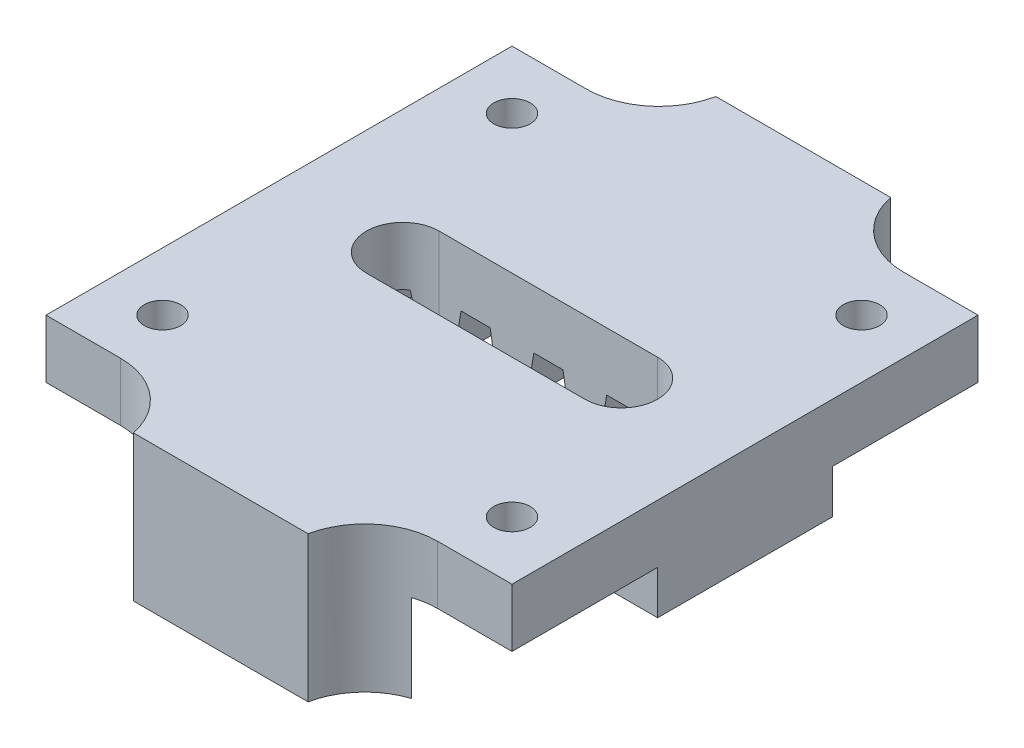
SolidWorks part; units mm, degrees
material "PBT Общее назначение"
ref_plane "Спереди" through (0, 0, 0) normal (0, 0, 1) x (1, 0, 0)
ref_plane "Сверху" through (0, 0, 0) normal (0, 1, 0) x (1, 0, 0)
ref_plane "Справа" through (0, 0, 0) normal (1, 0, 0) x (0, 0, -1)
sketch "Эскиз1" plane through (0, 0, 0) normal (0, 1, 0) x (1, 0, 0)
  line L0 (0, 0) -> (32, 0)
  line L1 (0, 0) -> (0, 32)
  line L2 (32, 0) -> (32, 32)
  line L3 (0, 32) -> (32, 32)
  dimension "D1" = 32
  dimension "D2" = 32
extrude "Бобышка-Вытянуть1" add sketch "Эскиз1" along normal blind 7
sketch "Эскиз3" plane through (0, 7, 0) normal (0, 1, 0) x (1, 0, 0)
  line L0 (16, 32) -> (16, 0) construction
  line L1 (32, 32) -> (0, 32) construction
  line L2 (0, 0) -> (32, 0) construction
  line L3 (32, 16) -> (0, 16) construction
  line L4 (32, 0) -> (32, 32) construction
  line L5 (0, 32) -> (0, 0) construction
  line L6 (4, 28) -> (28, 28) construction
  line L7 (4, 28) -> (4, 4) construction
  line L8 (28, 28) -> (28, 4) construction
  line L9 (4, 4) -> (28, 4) construction
  circle A0 centre (4, 28) radius 1.25
  circle A1 centre (28, 28) radius 1.25
  circle A2 centre (4, 4) radius 1.25
  circle A3 centre (28, 4) radius 1.25
  point P12 (16, 28)
  point P15 (28, 16)
  dimension "D3" = 2.5
  dimension "D1" = 24
  dimension "D2" = 24
extrude "Вырез-Вытянуть1" cut sketch "Эскиз3" against normal through all
sketch "Эскиз4" plane through (0, 0, 0) normal (0, -1, 0) x (1, 0, 0)
  line L0 (16, 0) -> (16, -32) construction
  line L1 (0, 0) -> (32, 0) construction
  line L2 (32, -32) -> (0, -32) construction
  line L3 (32, -16) -> (0, -16) construction
  line L4 (32, 0) -> (32, -32) construction
  line L5 (0, -32) -> (0, 0) construction
  line L6 (28, -10) -> (32, -10)
  line L7 (22, -4) -> (22, 0)
  line L8 (32, 0) -> (32, -10)
  line L9 (4, -10) -> (0, -10)
  line L10 (22, 0) -> (32, 0)
  line L11 (0, 0) -> (0, -10)
  line L12 (10, -4) -> (10, 0)
  line L13 (10, 0) -> (0, 0)
  line L14 (22, -32) -> (32, -32)
  line L15 (32, -32) -> (32, -22)
  line L16 (22, -28) -> (22, -32)
  line L17 (28, -22) -> (32, -22)
  line L18 (10, -32) -> (0, -32)
  line L19 (10, -28) -> (10, -32)
  line L20 (0, -32) -> (0, -22)
  line L21 (4, -22) -> (0, -22)
  arc A0 (22, -4) -> (28, -10) centre (28, -4) ccw
  arc A1 (10, -4) -> (4, -10) centre (4, -4) cw
  arc A2 (22, -28) -> (28, -22) centre (28, -28) cw
  arc A3 (10, -28) -> (4, -22) centre (4, -28) ccw
  dimension "D1" = 12
extrude "Вырез-Вытянуть2" cut sketch "Эскиз4" against normal blind 3
sketch "Эскиз5" plane through (0, 7, 0) normal (0, 1, 0) x (1, 0, 0)
  line L0 (16, 32) -> (16, 0) construction
  line L1 (32, 32) -> (0, 32) construction
  line L2 (0, 0) -> (32, 0) construction
  line L3 (32, 16) -> (0, 16) construction
  line L4 (32, 0) -> (32, 32) construction
  line L5 (0, 32) -> (0, 0) construction
  line L6 (23.5, 18.5) -> (8.5, 18.5)
  line L9 (23.5, 13.5) -> (8.5, 13.5)
  circle A0 centre (16, 16) radius 2.5 construction
  arc A1 (23.5, 13.5) -> (23.5, 18.5) centre (23.5, 16) ccw
  arc A2 (8.5, 18.5) -> (8.5, 13.5) centre (8.5, 16) ccw
  dimension "D1" = 5
  dimension "D2" = 7.5
  dimension "D3" = 7.5
extrude "Вырез-Вытянуть3" cut sketch "Эскиз5" against normal through all
sketch "Эскиз6" plane through (0, 0, 0) normal (0, 0, 1) x (1, 0, 0)
  line L0 (10, 7) -> (22, 7)
  line L1 (10, 7) -> (10, -3)
  line L2 (22, 7) -> (22, -3)
  line L3 (10, -3) -> (22, -3)
  line L4 (0, 7) -> (32, 7) construction
  line L5 (10, 3) -> (10, 0) construction
  line L6 (22, 3) -> (22, 0) construction
  line L7 (10, 0) -> (22, 0) construction
  dimension "D1" = 3
extrude "Бобышка-Вытянуть2" add sketch "Эскиз6" along normal blind 4
sketch "Эскиз7" plane through (0, 7, 0) normal (0, 1, 0) x (1, 0, 0)
  line L0 (32, 16) -> (0, 16) construction
  line L1 (32, 0) -> (32, 32) construction
  line L2 (0, 32) -> (0, 0) construction
ref_plane "Плоскость1" through (0, 0, -16) normal (0, 0, -1) x (-1, 0, 0)
mirror "Зеркальное отражение1" about plane through (0, 0, -16) normal (0, 0, -1) of "Бобышка-Вытянуть2"
sketch "Эскиз9" plane through (0, 7, 0) normal (0, 1, 0) x (1, 0, 0)
  line L0 (23.5, 16) -> (8.5, 16) construction
  line L1 (23.5, 10) -> (8.5, 10)
  line L2 (23.5, 22) -> (8.5, 22)
  arc A0 (23.5, 10) -> (23.5, 22) centre (23.5, 16) ccw
  arc A1 (8.5, 22) -> (8.5, 10) centre (8.5, 16) ccw
  arc A2 (8.5, 18.5) -> (8.5, 13.5) centre (8.5, 16) ccw construction
  point P3 (16, 16)
  dimension "D1" = 12
sketch "Эскиз10" plane through (0, 0, -16) normal (0, 0, -1) x (-1, 0, 0)
  line L1 (0, 0) -> (-4, 0) construction
  line L2 (0, 0) -> (-32, 0) construction
  line L4 (-16, 0) -> (-16, 31.1305) construction
  line L5 (-14.5, 0) -> (-15, 3)
  line L6 (-15, 3) -> (-17, 3)
  line L7 (-14.5, 0) -> (-17.5, 0)
  line L8 (-17.5, 0) -> (-17, 3)
  line L9 (-9.5, 0) -> (-10, 3)
  line L10 (-10, 3) -> (-12, 3)
  line L11 (-9.5, 0) -> (-12.5, 0)
  line L12 (-12.5, 0) -> (-12, 3)
  line L13 (-4.5, 0) -> (-5, 3)
  line L14 (-5, 3) -> (-7, 3)
  line L15 (-4.5, 0) -> (-7.5, 0)
  line L16 (-7.5, 0) -> (-7, 3)
  line L17 (-22.5, 0) -> (-22, 3)
  line L18 (-19.5, 0) -> (-22.5, 0)
  line L19 (-19.5, 0) -> (-20, 3)
  line L20 (-20, 3) -> (-22, 3)
  line L21 (-27.5, 0) -> (-27, 3)
  line L22 (-24.5, 0) -> (-27.5, 0)
  line L23 (-24.5, 0) -> (-25, 3)
  line L24 (-25, 3) -> (-27, 3)
  point P10 (-16, 3)
  point P16 (-11, 3)
  point P21 (-6, 3)
  dimension "D1" = 1.5
  dimension "D2" = 1
  dimension "D3" = 3
  dimension "D5" = 5
  dimension "D7" = 5
  dimension "D4" = 3
  dimension "D6" = 3
sketch "Эскиз11" plane through (0, 0, 0) normal (0, 0, -1) x (-1, 0, 0)
  line L4 (-10, -3) -> (-10, 0)
  line L5 (-10, 0) -> (-22, 0)
  line L6 (-22, 0) -> (-22, -3)
  line L7 (-22, -3) -> (-10, -3)
  line L8 (-10, -3) -> (-10, 0)
  line L9 (-10, 0) -> (-22, 0)
  line L10 (-22, 0) -> (-22, -3)
  line L11 (-22, -3) -> (-10, -3)
  dimension "D1" = 0
extrude "Вырез-Вытянуть5" cut sketch "Эскиз11" against normal blind 0.25
sketch "Эскиз12" plane through (0, 0, -32) normal (0, 0, 1) x (1, 0, 0)
  line L4 (22, -3) -> (22, 0)
  line L5 (22, 0) -> (10, 0)
  line L6 (10, 0) -> (10, -3)
  line L7 (10, -3) -> (22, -3)
  line L8 (22, -3) -> (22, 0)
  line L9 (22, 0) -> (10, 0)
  line L10 (10, 0) -> (10, -3)
  line L11 (10, -3) -> (22, -3)
  dimension "D1" = 0
extrude "Вырез-Вытянуть6" cut sketch "Эскиз12" against normal blind 0.25
extrude "Вырез-Вытянуть7" cut sketch "Эскиз10" against normal up to surface and the other way up to surface up to face at (16, -1.5, 0.25) other way up to face at (16, -1.5, -32.25)
fillet "Скругление1" radius 5 1 edges
fillet "Скругление2" radius 5 3 edges
sketch "Эскиз13" plane through (0, 0, 0) normal (-1, 0, 0) x (0, 0, 1)
  line L0 (-10, 3) -> (-10, 0) construction
  line L1 (0, 3) -> (-10, 3) construction
  line L2 (-10, 3) -> (-10, 0)
  line L3 (0, 3) -> (-10, 3)
  line L4 (-10, 0) -> (0, 0)
  line L5 (0, 3) -> (0, 0)
extrude "Вырез-Вытянуть8" cut sketch "Эскиз13" against normal up to surface (12.5 mm away) up to face at (12.25, 1.5, -6.625)
sketch "Эскиз14" plane through (32, 0, 0) normal (1, 0, 0) x (0, 0, -1)
  line L0 (10, 3) -> (0, 3) construction
  line L1 (10, 3) -> (10, 0) construction
  line L2 (10, 3) -> (0, 3)
  line L3 (10, 3) -> (10, 0)
  line L4 (10, 0) -> (0, 0)
  line L5 (0, 0) -> (0, 3)
extrude "Вырез-Вытянуть9" cut sketch "Эскиз14" against normal up to surface (12 mm away) up to face at (19.75, 1.5, -6.625)
mirror "Зеркальное отражение2" about plane through (0, 0, -16) normal (0, 0, -1) of "Вырез-Вытянуть9", "Вырез-Вытянуть8"
sketch "Эскиз15" plane through (0, 7, 0) normal (0, 1, 0) x (1, 0, 0)
  line L0 (16, 36) -> (16, -4) construction
  line L1 (22, 36) -> (10, 36) construction
  line L2 (22, -4) -> (10, -4) construction
ref_plane "Плоскость2" through (16, 0, 0) normal (-1, 0, 0) x (0, 0, 1)
